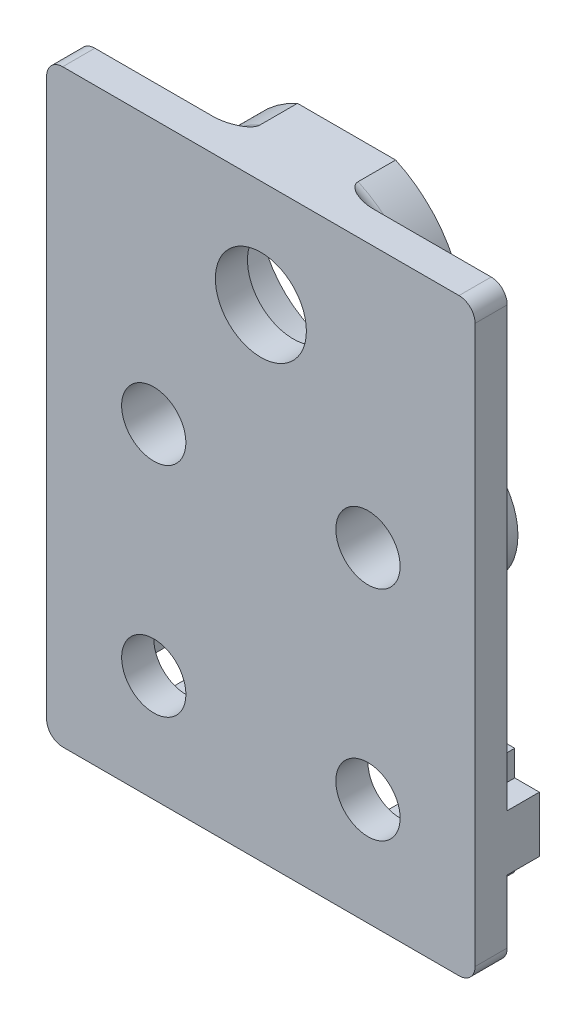
SolidWorks part; units mm, degrees
ref_plane "前视基准面" through (0, 0, 0) normal (0, 0, 1) x (1, 0, 0)
ref_plane "上视基准面" through (0, 0, 0) normal (0, 1, 0) x (1, 0, 0)
ref_plane "右视基准面" through (0, 0, 0) normal (1, 0, 0) x (0, 0, -1)
sketch "草图1" plane through (0, 0, 0) normal (0, 0, 1) x (1, 0, 0)
  line L0 (-20, 0) -> (-20, -6.9)
  line L1 (-20, 0) -> (-13.1, 0)
  line L4 (-6.9, -1.8) -> (-6.9, 0)
  line L5 (-13.1, -1.8) -> (-13.1, 0)
  line L6 (-4.5, -3.4393) -> (-4.5, -1.8)
  line L7 (-4.5, -3.4393) -> (-7.1607, -6.1)
  line L8 (-3.4393, -4.5) -> (-6.1, -7.1607)
  line L9 (-16.5607, -4.5) -> (-18.2, -4.5)
  line L10 (-13.1, -1.8) -> (-15.5, -1.8)
  line L11 (-6.9, 0) -> (0, 0)
  line L12 (-12.8393, -13.9) -> (-7.1607, -13.9)
  line L13 (-13.9, -12.8393) -> (-13.9, -7.1607)
  line L14 (-12.8393, -6.1) -> (-7.1607, -6.1)
  line L15 (-6.1, -12.8393) -> (-6.1, -7.1607)
  line L16 (-10, -6.1) -> (-10, -13.9) construction
  line L17 (-13.9, -10) -> (-6.1, -10) construction
  line L18 (-6.9, -1.8) -> (-4.5, -1.8)
  line L19 (-16.5607, -4.5) -> (-13.9, -7.1607)
  line L20 (-15.5, -3.4393) -> (-12.8393, -6.1)
  line L21 (-15.5, -3.4393) -> (-15.5, -1.8)
  line L22 (-18.2, -6.9) -> (-18.2, -4.5)
  line L23 (-18.2, -6.9) -> (-20, -6.9)
  line L24 (-18.2, -13.1) -> (-20, -13.1)
  line L25 (-18.2, -13.1) -> (-18.2, -15.5)
  line L26 (-15.5, -16.5607) -> (-15.5, -18.2)
  line L27 (-15.5, -16.5607) -> (-12.8393, -13.9)
  line L28 (-16.5607, -15.5) -> (-13.9, -12.8393)
  line L29 (-6.9, -18.2) -> (-4.5, -18.2)
  line L30 (-6.9, -20) -> (0, -20)
  line L31 (-13.1, -18.2) -> (-15.5, -18.2)
  line L32 (-16.5607, -15.5) -> (-18.2, -15.5)
  line L33 (-3.4393, -15.5) -> (-6.1, -12.8393)
  line L34 (-4.5, -16.5607) -> (-7.1607, -13.9)
  line L35 (-4.5, -16.5607) -> (-4.5, -18.2)
  line L36 (-13.1, -18.2) -> (-13.1, -20)
  line L37 (-6.9, -18.2) -> (-6.9, -20)
  line L38 (-20, -20) -> (-13.1, -20)
  line L39 (-20, -20) -> (-20, -13.1)
  line L40 (0, 0) -> (6.9, 0)
  line L41 (18.2, -6.9) -> (20, -6.9)
  line L42 (13.1, -1.8) -> (13.1, 0)
  line L43 (6.9, -1.8) -> (6.9, 0)
  line L44 (20, 0) -> (20, -6.9)
  line L45 (18.2, -6.9) -> (18.2, -4.5)
  line L46 (15.5, -3.4393) -> (15.5, -1.8)
  line L47 (15.5, -3.4393) -> (12.8393, -6.1)
  line L48 (16.5607, -4.5) -> (13.9, -7.1607)
  line L49 (6.9, -1.8) -> (4.5, -1.8)
  line L50 (13.1, 0) -> (20, 0)
  line L51 (7.1607, -13.9) -> (12.8393, -13.9)
  line L52 (6.1, -12.8393) -> (6.1, -7.1607)
  line L53 (7.1607, -6.1) -> (12.8393, -6.1)
  line L54 (13.9, -12.8393) -> (13.9, -7.1607)
  line L55 (13.1, -1.8) -> (15.5, -1.8)
  line L56 (16.5607, -4.5) -> (18.2, -4.5)
  line L57 (3.4393, -4.5) -> (6.1, -7.1607)
  line L58 (4.5, -3.4393) -> (7.1607, -6.1)
  line L59 (4.5, -3.4393) -> (4.5, -1.8)
  line L60 (4.5, -16.5607) -> (4.5, -18.2)
  line L61 (4.5, -16.5607) -> (7.1607, -13.9)
  line L62 (3.4393, -15.5) -> (6.1, -12.8393)
  line L63 (16.5607, -15.5) -> (18.2, -15.5)
  line L64 (13.1, -18.2) -> (15.5, -18.2)
  line L65 (13.1, -20) -> (20, -20)
  line L66 (6.9, -18.2) -> (4.5, -18.2)
  line L67 (16.5607, -15.5) -> (13.9, -12.8393)
  line L68 (15.5, -16.5607) -> (12.8393, -13.9)
  line L69 (15.5, -16.5607) -> (15.5, -18.2)
  line L70 (18.2, -13.1) -> (18.2, -15.5)
  line L71 (20, -20) -> (20, -13.1)
  line L72 (6.9, -18.2) -> (6.9, -20)
  line L73 (13.1, -18.2) -> (13.1, -20)
  line L74 (18.2, -13.1) -> (20, -13.1)
  line L75 (0, -20) -> (6.9, -20)
  line L78 (10, -6.1) -> (10, -13.9) construction
  line L79 (6.1, -10) -> (13.9, -10) construction
  line L80 (3.4393, -1.8) -> (-3.4393, -1.8)
  line L81 (-3.4393, -1.8) -> (-3.4393, -4.5)
  line L82 (3.4393, -1.8) -> (3.4393, -4.5)
  line L83 (-3.4393, -18.2) -> (-3.4393, -15.5)
  line L84 (3.4393, -18.2) -> (3.4393, -15.5)
  line L85 (3.4393, -18.2) -> (-3.4393, -18.2)
  circle A0 centre (-10, -10) radius 2.55
  circle A1 centre (10, -10) radius 2.55
  point P0 (-10, -10)
  point P8 (-10, -1.8)
  point P9 (-9.8043, -1.8)
  point P13 (-10, -1.8)
  point P20 (-5, -5)
  point P33 (-15, -5)
  point P50 (-15, -15)
  point P51 (-5, -15)
  point P52 (-10, -18.2)
  point P53 (-9.8043, -18.2)
  point P54 (10, -10)
  point P58 (10, -1.8)
  point P59 (10.1957, -1.8)
  point P63 (10, -1.8)
  point P70 (15, -5)
  point P83 (5, -5)
  point P102 (5, -15)
  point P103 (15, -15)
  point P104 (10, -18.2)
  point P105 (10.1957, -18.2)
extrude "凸台-拉伸1" add sketch "草图1" along normal blind 10
sketch "草图2" plane through (0, 0, 10) normal (0, 0, 1) x (1, 0, 0)
  line L1 (-20, 0) -> (20, 0)
  line L2 (-20, 0) -> (-20, -20)
  line L3 (-20, -20) -> (20, -20)
  line L4 (20, 0) -> (20, -20)
extrude "凸台-拉伸2" add sketch "草图2" along normal blind 3
sketch "草图3" plane through (0, 0, 10) normal (0, 0, -1) x (-1, 0, 0)
  line L0 (-13.1, -20) -> (-6.9, -20) construction
  line L1 (-6.9, -20) -> (-6.9, -18.2) construction
  line L2 (-6.9, -18.2) -> (-4.5, -18.2) construction
  line L3 (-4.5, -18.2) -> (-4.5, -16.5607) construction
  line L4 (-4.5, -16.5607) -> (-7.1607, -13.9) construction
  line L5 (-7.1607, -13.9) -> (-12.8393, -13.9) construction
  line L6 (-12.8393, -13.9) -> (-15.5, -16.5607) construction
  line L7 (-15.5, -16.5607) -> (-15.5, -18.2) construction
  line L8 (-15.5, -18.2) -> (-13.1, -18.2) construction
  line L9 (-13.1, -18.2) -> (-13.1, -20) construction
  line L10 (-20, -6.9) -> (-20, -13.1) construction
  line L11 (-20, -13.1) -> (-18.2, -13.1) construction
  line L12 (-18.2, -13.1) -> (-18.2, -15.5) construction
  line L13 (-18.2, -15.5) -> (-16.5607, -15.5) construction
  line L14 (-16.5607, -15.5) -> (-13.9, -12.8393) construction
  line L15 (-13.9, -12.8393) -> (-13.9, -7.1607) construction
  line L16 (-13.9, -7.1607) -> (-16.5607, -4.5) construction
  line L17 (-16.5607, -4.5) -> (-18.2, -4.5) construction
  line L18 (-18.2, -4.5) -> (-18.2, -6.9) construction
  line L19 (-18.2, -6.9) -> (-20, -6.9) construction
  line L20 (-6.9, 0) -> (-13.1, 0) construction
  line L21 (-13.1, 0) -> (-13.1, -1.8) construction
  line L22 (-13.1, -1.8) -> (-15.5, -1.8) construction
  line L23 (-15.5, -1.8) -> (-15.5, -3.4393) construction
  line L24 (-15.5, -3.4393) -> (-12.8393, -6.1) construction
  line L25 (-12.8393, -6.1) -> (-7.1607, -6.1) construction
  line L26 (-7.1607, -6.1) -> (-4.5, -3.4393) construction
  line L27 (-4.5, -3.4393) -> (-4.5, -1.8) construction
  line L28 (-4.5, -1.8) -> (-6.9, -1.8) construction
  line L29 (-6.9, -1.8) -> (-6.9, 0) construction
  line L30 (6.9, -20) -> (13.1, -20) construction
  line L31 (13.1, -20) -> (13.1, -18.2) construction
  line L32 (13.1, -18.2) -> (15.5, -18.2) construction
  line L33 (15.5, -18.2) -> (15.5, -16.5607) construction
  line L34 (15.5, -16.5607) -> (12.8393, -13.9) construction
  line L35 (12.8393, -13.9) -> (7.1607, -13.9) construction
  line L36 (7.1607, -13.9) -> (4.5, -16.5607) construction
  line L37 (4.5, -16.5607) -> (4.5, -18.2) construction
  line L38 (4.5, -18.2) -> (6.9, -18.2) construction
  line L39 (6.9, -18.2) -> (6.9, -20) construction
  line L40 (20, -13.1) -> (20, -6.9) construction
  line L41 (20, -6.9) -> (18.2, -6.9) construction
  line L42 (18.2, -6.9) -> (18.2, -4.5) construction
  line L43 (18.2, -4.5) -> (16.5607, -4.5) construction
  line L44 (16.5607, -4.5) -> (13.9, -7.1607) construction
  line L45 (13.9, -7.1607) -> (13.9, -12.8393) construction
  line L46 (13.9, -12.8393) -> (16.5607, -15.5) construction
  line L47 (16.5607, -15.5) -> (18.2, -15.5) construction
  line L48 (18.2, -15.5) -> (18.2, -13.1) construction
  line L49 (18.2, -13.1) -> (20, -13.1) construction
  line L50 (13.1, 0) -> (6.9, 0) construction
  line L51 (6.9, 0) -> (6.9, -1.8) construction
  line L52 (6.9, -1.8) -> (4.5, -1.8) construction
  line L53 (4.5, -1.8) -> (4.5, -3.4393) construction
  line L54 (4.5, -3.4393) -> (7.1607, -6.1) construction
  line L55 (7.1607, -6.1) -> (12.8393, -6.1) construction
  line L56 (12.8393, -6.1) -> (15.5, -3.4393) construction
  line L57 (15.5, -3.4393) -> (15.5, -1.8) construction
  line L58 (15.5, -1.8) -> (13.1, -1.8) construction
  line L59 (13.1, -1.8) -> (13.1, 0) construction
  line L60 (-13.1, -20) -> (-6.9, -20)
  line L61 (-6.9, -20) -> (-6.9, -18.2)
  line L62 (-6.9, -18.2) -> (-4.5, -18.2)
  line L63 (-4.5, -18.2) -> (-4.5, -16.5607)
  line L64 (-4.5, -16.5607) -> (-7.1607, -13.9)
  line L65 (-7.1607, -13.9) -> (-12.8393, -13.9)
  line L66 (-12.8393, -13.9) -> (-15.5, -16.5607)
  line L67 (-15.5, -16.5607) -> (-15.5, -18.2)
  line L68 (-15.5, -18.2) -> (-13.1, -18.2)
  line L69 (-13.1, -18.2) -> (-13.1, -20)
  line L70 (-20, -6.9) -> (-20, -13.1)
  line L71 (-20, -13.1) -> (-18.2, -13.1)
  line L72 (-18.2, -13.1) -> (-18.2, -15.5)
  line L73 (-18.2, -15.5) -> (-16.5607, -15.5)
  line L74 (-16.5607, -15.5) -> (-13.9, -12.8393)
  line L75 (-13.9, -12.8393) -> (-13.9, -7.1607)
  line L76 (-13.9, -7.1607) -> (-16.5607, -4.5)
  line L77 (-16.5607, -4.5) -> (-18.2, -4.5)
  line L78 (-18.2, -4.5) -> (-18.2, -6.9)
  line L79 (-18.2, -6.9) -> (-20, -6.9)
  line L80 (-6.9, 0) -> (-13.1, 0)
  line L81 (-13.1, 0) -> (-13.1, -1.8)
  line L82 (-13.1, -1.8) -> (-15.5, -1.8)
  line L83 (-15.5, -1.8) -> (-15.5, -3.4393)
  line L84 (-15.5, -3.4393) -> (-12.8393, -6.1)
  line L85 (-12.8393, -6.1) -> (-7.1607, -6.1)
  line L86 (-7.1607, -6.1) -> (-4.5, -3.4393)
  line L87 (-4.5, -3.4393) -> (-4.5, -1.8)
  line L88 (-4.5, -1.8) -> (-6.9, -1.8)
  line L89 (-6.9, -1.8) -> (-6.9, 0)
  line L90 (6.9, -20) -> (13.1, -20)
  line L91 (13.1, -20) -> (13.1, -18.2)
  line L92 (13.1, -18.2) -> (15.5, -18.2)
  line L93 (15.5, -18.2) -> (15.5, -16.5607)
  line L94 (15.5, -16.5607) -> (12.8393, -13.9)
  line L95 (12.8393, -13.9) -> (7.1607, -13.9)
  line L96 (7.1607, -13.9) -> (4.5, -16.5607)
  line L97 (4.5, -16.5607) -> (4.5, -18.2)
  line L98 (4.5, -18.2) -> (6.9, -18.2)
  line L99 (6.9, -18.2) -> (6.9, -20)
  line L100 (20, -13.1) -> (20, -6.9)
  line L101 (20, -6.9) -> (18.2, -6.9)
  line L102 (18.2, -6.9) -> (18.2, -4.5)
  line L103 (18.2, -4.5) -> (16.5607, -4.5)
  line L104 (16.5607, -4.5) -> (13.9, -7.1607)
  line L105 (13.9, -7.1607) -> (13.9, -12.8393)
  line L106 (13.9, -12.8393) -> (16.5607, -15.5)
  line L107 (16.5607, -15.5) -> (18.2, -15.5)
  line L108 (18.2, -15.5) -> (18.2, -13.1)
  line L109 (18.2, -13.1) -> (20, -13.1)
  line L110 (13.1, 0) -> (6.9, 0)
  line L111 (6.9, 0) -> (6.9, -1.8)
  line L112 (6.9, -1.8) -> (4.5, -1.8)
  line L113 (4.5, -1.8) -> (4.5, -3.4393)
  line L114 (4.5, -3.4393) -> (7.1607, -6.1)
  line L115 (7.1607, -6.1) -> (12.8393, -6.1)
  line L116 (12.8393, -6.1) -> (15.5, -3.4393)
  line L117 (15.5, -3.4393) -> (15.5, -1.8)
  line L118 (15.5, -1.8) -> (13.1, -1.8)
  line L119 (13.1, -1.8) -> (13.1, 0)
extrude "凸台-拉伸3" add sketch "草图3" along normal blind 3
sketch "草图4" plane through (0, 0, 0) normal (0, 0, -1) x (-1, 0, 0)
  line L64 (6.9, 0) -> (-6.9, 0)
  line L65 (-6.9, 0) -> (-6.9, -1.8)
  line L66 (-6.9, -1.8) -> (-4.5, -1.8)
  line L67 (-4.5, -1.8) -> (-4.5, -3.4393)
  line L68 (-4.5, -3.4393) -> (-7.1607, -6.1)
  line L69 (-7.1607, -6.1) -> (-12.8393, -6.1)
  line L70 (-12.8393, -6.1) -> (-15.5, -3.4393)
  line L71 (-15.5, -3.4393) -> (-15.5, -1.8)
  line L72 (-15.5, -1.8) -> (-13.1, -1.8)
  line L73 (-13.1, -1.8) -> (-13.1, 0)
  line L74 (-13.1, 0) -> (-20, 0)
  line L75 (-20, 0) -> (-20, -6.9)
  line L76 (-20, -6.9) -> (-18.2, -6.9)
  line L77 (-18.2, -6.9) -> (-18.2, -4.5)
  line L78 (-18.2, -4.5) -> (-16.5607, -4.5)
  line L79 (-16.5607, -4.5) -> (-13.9, -7.1607)
  line L80 (-13.9, -7.1607) -> (-13.9, -12.8393)
  line L81 (-13.9, -12.8393) -> (-16.5607, -15.5)
  line L82 (-16.5607, -15.5) -> (-18.2, -15.5)
  line L83 (-18.2, -15.5) -> (-18.2, -13.1)
  line L84 (-18.2, -13.1) -> (-20, -13.1)
  line L85 (-20, -13.1) -> (-20, -20)
  line L86 (-20, -20) -> (-13.1, -20)
  line L87 (-13.1, -20) -> (-13.1, -18.2)
  line L88 (-13.1, -18.2) -> (-15.5, -18.2)
  line L89 (-15.5, -18.2) -> (-15.5, -16.5607)
  line L90 (-15.5, -16.5607) -> (-12.8393, -13.9)
  line L91 (-12.8393, -13.9) -> (-7.1607, -13.9)
  line L92 (-7.1607, -13.9) -> (-4.5, -16.5607)
  line L93 (-4.5, -16.5607) -> (-4.5, -18.2)
  line L94 (-4.5, -18.2) -> (-6.9, -18.2)
  line L95 (-6.9, -18.2) -> (-6.9, -20)
  line L96 (-6.9, -20) -> (6.9, -20)
  line L97 (6.9, -20) -> (6.9, -18.2)
  line L98 (6.9, -18.2) -> (4.5, -18.2)
  line L99 (4.5, -18.2) -> (4.5, -16.5607)
  line L100 (4.5, -16.5607) -> (7.1607, -13.9)
  line L101 (7.1607, -13.9) -> (12.8393, -13.9)
  line L102 (12.8393, -13.9) -> (15.5, -16.5607)
  line L103 (15.5, -16.5607) -> (15.5, -18.2)
  line L104 (15.5, -18.2) -> (13.1, -18.2)
  line L105 (13.1, -18.2) -> (13.1, -20)
  line L106 (13.1, -20) -> (20, -20)
  line L107 (20, -20) -> (20, -13.1)
  line L108 (20, -13.1) -> (18.2, -13.1)
  line L109 (18.2, -13.1) -> (18.2, -15.5)
  line L110 (18.2, -15.5) -> (16.5607, -15.5)
  line L111 (16.5607, -15.5) -> (13.9, -12.8393)
  line L112 (13.9, -12.8393) -> (13.9, -7.1607)
  line L113 (13.9, -7.1607) -> (16.5607, -4.5)
  line L114 (16.5607, -4.5) -> (18.2, -4.5)
  line L115 (18.2, -4.5) -> (18.2, -6.9)
  line L116 (18.2, -6.9) -> (20, -6.9)
  line L117 (20, -6.9) -> (20, 0)
  line L118 (20, 0) -> (13.1, 0)
  line L119 (13.1, 0) -> (13.1, -1.8)
  line L120 (13.1, -1.8) -> (15.5, -1.8)
  line L121 (15.5, -1.8) -> (15.5, -3.4393)
  line L122 (15.5, -3.4393) -> (12.8393, -6.1)
  line L123 (12.8393, -6.1) -> (7.1607, -6.1)
  line L124 (7.1607, -6.1) -> (4.5, -3.4393)
  line L125 (4.5, -3.4393) -> (4.5, -1.8)
  line L126 (4.5, -1.8) -> (6.9, -1.8)
  line L127 (6.9, -1.8) -> (6.9, 0)
  line L128 (6.9, 0) -> (-6.9, 0)
  line L129 (-6.9, 0) -> (-6.9, -1.8)
  line L130 (-6.9, -1.8) -> (-4.5, -1.8)
  line L131 (-4.5, -1.8) -> (-4.5, -3.4393)
  line L132 (-4.5, -3.4393) -> (-7.1607, -6.1)
  line L133 (-7.1607, -6.1) -> (-12.8393, -6.1)
  line L134 (-12.8393, -6.1) -> (-15.5, -3.4393)
  line L135 (-15.5, -3.4393) -> (-15.5, -1.8)
  line L136 (-15.5, -1.8) -> (-13.1, -1.8)
  line L137 (-13.1, -1.8) -> (-13.1, 0)
  line L138 (-13.1, 0) -> (-20, 0)
  line L139 (-20, 0) -> (-20, -6.9)
  line L140 (-20, -6.9) -> (-18.2, -6.9)
  line L141 (-18.2, -6.9) -> (-18.2, -4.5)
  line L142 (-18.2, -4.5) -> (-16.5607, -4.5)
  line L143 (-16.5607, -4.5) -> (-13.9, -7.1607)
  line L144 (-13.9, -7.1607) -> (-13.9, -12.8393)
  line L145 (-13.9, -12.8393) -> (-16.5607, -15.5)
  line L146 (-16.5607, -15.5) -> (-18.2, -15.5)
  line L147 (-18.2, -15.5) -> (-18.2, -13.1)
  line L148 (-18.2, -13.1) -> (-20, -13.1)
  line L149 (-20, -13.1) -> (-20, -20)
  line L150 (-20, -20) -> (-13.1, -20)
  line L151 (-13.1, -20) -> (-13.1, -18.2)
  line L152 (-13.1, -18.2) -> (-15.5, -18.2)
  line L153 (-15.5, -18.2) -> (-15.5, -16.5607)
  line L154 (-15.5, -16.5607) -> (-12.8393, -13.9)
  line L155 (-12.8393, -13.9) -> (-7.1607, -13.9)
  line L156 (-7.1607, -13.9) -> (-4.5, -16.5607)
  line L157 (-4.5, -16.5607) -> (-4.5, -18.2)
  line L158 (-4.5, -18.2) -> (-6.9, -18.2)
  line L159 (-6.9, -18.2) -> (-6.9, -20)
  line L160 (-6.9, -20) -> (6.9, -20)
  line L161 (6.9, -20) -> (6.9, -18.2)
  line L162 (6.9, -18.2) -> (4.5, -18.2)
  line L163 (4.5, -18.2) -> (4.5, -16.5607)
  line L164 (4.5, -16.5607) -> (7.1607, -13.9)
  line L165 (7.1607, -13.9) -> (12.8393, -13.9)
  line L166 (12.8393, -13.9) -> (15.5, -16.5607)
  line L167 (15.5, -16.5607) -> (15.5, -18.2)
  line L168 (15.5, -18.2) -> (13.1, -18.2)
  line L169 (13.1, -18.2) -> (13.1, -20)
  line L170 (13.1, -20) -> (20, -20)
  line L171 (20, -20) -> (20, -13.1)
  line L172 (20, -13.1) -> (18.2, -13.1)
  line L173 (18.2, -13.1) -> (18.2, -15.5)
  line L174 (18.2, -15.5) -> (16.5607, -15.5)
  line L175 (16.5607, -15.5) -> (13.9, -12.8393)
  line L176 (13.9, -12.8393) -> (13.9, -7.1607)
  line L177 (13.9, -7.1607) -> (16.5607, -4.5)
  line L178 (16.5607, -4.5) -> (18.2, -4.5)
  line L179 (18.2, -4.5) -> (18.2, -6.9)
  line L180 (18.2, -6.9) -> (20, -6.9)
  line L181 (20, -6.9) -> (20, 0)
  line L182 (20, 0) -> (13.1, 0)
  line L183 (13.1, 0) -> (13.1, -1.8)
  line L184 (13.1, -1.8) -> (15.5, -1.8)
  line L185 (15.5, -1.8) -> (15.5, -3.4393)
  line L186 (15.5, -3.4393) -> (12.8393, -6.1)
  line L187 (12.8393, -6.1) -> (7.1607, -6.1)
  line L188 (7.1607, -6.1) -> (4.5, -3.4393)
  line L189 (4.5, -3.4393) -> (4.5, -1.8)
  line L190 (4.5, -1.8) -> (6.9, -1.8)
  line L191 (6.9, -1.8) -> (6.9, 0)
  dimension "D1" = 0
extrude "切除-拉伸1" cut sketch "草图4" against normal blind 10
sketch "草图5" plane through (0, 0, 10) normal (0, 0, -1) x (-1, 0, 0)
  circle A0 centre (-10, -10) radius 3
  circle A1 centre (10, -10) radius 3
extrude "切除-拉伸2" cut sketch "草图5" against normal blind 10
sketch "草图6" plane through (0, 0, 13) normal (0, 0, 1) x (1, 0, 0)
  line L0 (-20, 0) -> (20, 0)
  line L1 (0, 35) -> (-20, 35)
  line L2 (-20, 35) -> (-20, 0)
  line L3 (20, 0) -> (20, 35)
  line L4 (0, 35) -> (20, 35)
  circle A0 centre (-10, 10.36) radius 3
  circle A1 centre (10, 10.36) radius 3
  circle A2 centre (0, 25) radius 4.25
extrude "凸台-拉伸4" add sketch "草图6" against normal blind 3
fillet "圆角1" radius 1.5 4 edges at (-20, -20, 11.5) (-20, 35, 11.5) (20, -20, 11.5) (20, 35, 11.5)
sketch "草图7" plane through (0, 0, 10) normal (0, 0, -1) x (-1, 0, 0)
  circle A1 centre (10, 10.36) radius 3 construction
  circle A2 centre (-10, 10.36) radius 3 construction
  circle A4 centre (10, 10.36) radius 3
  circle A5 centre (-10, 10.36) radius 3
  circle A6 centre (-10, 10.36) radius 6
  circle A7 centre (10, 10.36) radius 6
  dimension "D1" = 3
extrude "凸台-拉伸5" add sketch "草图7" along normal blind 5
sketch "草图8" plane through (0, 0, 10) normal (0, 0, -1) x (-1, 0, 0)
  line L0 (-4.5826, 35) -> (4.5826, 35)
  line L1 (-18.5, 35) -> (18.5, 35) construction
  circle A0 centre (0, 25) radius 8.25
  arc A1 (-4.5826, 35) -> (4.5826, 35) centre (0, 25) ccw
extrude "凸台-拉伸6" add sketch "草图8" along normal blind 5
fillet "圆角3" radius 1.5 3 edges at (-4, 10.36, 10) (16, 10.36, 10) (0, 14, 10)
sketch "草图9" plane through (0, 0, 7) normal (0, 0, -1) x (-1, 0, 0)
  line L0 (6.9, -18.2) -> (6.9, -20) construction
  line L1 (6.9, -20) -> (13.1, -20) construction
  line L2 (13.1, -20) -> (13.1, -18.2) construction
  line L3 (13.1, -18.2) -> (15.5, -18.2) construction
  line L4 (15.5, -18.2) -> (15.5, -16.5607) construction
  line L5 (15.5, -16.5607) -> (12.8393, -13.9) construction
  line L6 (12.8393, -13.9) -> (7.1607, -13.9) construction
  line L7 (7.1607, -13.9) -> (4.5, -16.5607) construction
  line L8 (4.5, -16.5607) -> (4.5, -18.2) construction
  line L9 (4.5, -18.2) -> (6.9, -18.2) construction
  line L10 (18.2, -13.1) -> (20, -13.1) construction
  line L11 (20, -13.1) -> (20, -6.9) construction
  line L12 (20, -6.9) -> (18.2, -6.9) construction
  line L13 (18.2, -6.9) -> (18.2, -4.5) construction
  line L14 (18.2, -4.5) -> (16.5607, -4.5) construction
  line L15 (16.5607, -4.5) -> (13.9, -7.1607) construction
  line L16 (13.9, -7.1607) -> (13.9, -12.8393) construction
  line L17 (13.9, -12.8393) -> (16.5607, -15.5) construction
  line L18 (16.5607, -15.5) -> (18.2, -15.5) construction
  line L19 (18.2, -15.5) -> (18.2, -13.1) construction
  line L20 (13.1, -1.8) -> (13.1, 0) construction
  line L21 (13.1, 0) -> (6.9, 0) construction
  line L22 (6.9, 0) -> (6.9, -1.8) construction
  line L23 (6.9, -1.8) -> (4.5, -1.8) construction
  line L24 (4.5, -1.8) -> (4.5, -3.4393) construction
  line L25 (4.5, -3.4393) -> (7.1607, -6.1) construction
  line L26 (7.1607, -6.1) -> (12.8393, -6.1) construction
  line L27 (12.8393, -6.1) -> (15.5, -3.4393) construction
  line L28 (15.5, -3.4393) -> (15.5, -1.8) construction
  line L29 (15.5, -1.8) -> (13.1, -1.8) construction
  line L30 (-6.9, -1.8) -> (-6.9, 0) construction
  line L31 (-6.9, 0) -> (-13.1, 0) construction
  line L32 (-13.1, 0) -> (-13.1, -1.8) construction
  line L33 (-13.1, -1.8) -> (-15.5, -1.8) construction
  line L34 (-15.5, -1.8) -> (-15.5, -3.4393) construction
  line L35 (-15.5, -3.4393) -> (-12.8393, -6.1) construction
  line L36 (-12.8393, -6.1) -> (-7.1607, -6.1) construction
  line L37 (-7.1607, -6.1) -> (-4.5, -3.4393) construction
  line L38 (-4.5, -3.4393) -> (-4.5, -1.8) construction
  line L39 (-4.5, -1.8) -> (-6.9, -1.8) construction
  line L40 (-13.1, -18.2) -> (-13.1, -20) construction
  line L41 (-13.1, -20) -> (-6.9, -20) construction
  line L42 (-6.9, -20) -> (-6.9, -18.2) construction
  line L43 (-6.9, -18.2) -> (-4.5, -18.2) construction
  line L44 (-4.5, -18.2) -> (-4.5, -16.5607) construction
  line L45 (-4.5, -16.5607) -> (-7.1607, -13.9) construction
  line L46 (-7.1607, -13.9) -> (-12.8393, -13.9) construction
  line L47 (-12.8393, -13.9) -> (-15.5, -16.5607) construction
  line L48 (-15.5, -16.5607) -> (-15.5, -18.2) construction
  line L49 (-15.5, -18.2) -> (-13.1, -18.2) construction
  line L50 (-18.2, -6.9) -> (-20, -6.9) construction
  line L51 (-20, -6.9) -> (-20, -13.1) construction
  line L52 (-20, -13.1) -> (-18.2, -13.1) construction
  line L53 (-18.2, -13.1) -> (-18.2, -15.5) construction
  line L54 (-18.2, -15.5) -> (-16.5607, -15.5) construction
  line L55 (-16.5607, -15.5) -> (-13.9, -12.8393) construction
  line L56 (-13.9, -12.8393) -> (-13.9, -7.1607) construction
  line L57 (-13.9, -7.1607) -> (-16.5607, -4.5) construction
  line L58 (-16.5607, -4.5) -> (-18.2, -4.5) construction
  line L59 (-18.2, -4.5) -> (-18.2, -6.9) construction
  line L60 (6.9, -18.2) -> (6.9, -20)
  line L61 (6.9, -20) -> (7.4, -20)
  line L62 (13.1, -20) -> (13.1, -18.2)
  line L63 (13.1, -18.2) -> (15.5, -18.2)
  line L64 (15.5, -18.2) -> (15.5, -16.5607)
  line L65 (15.5, -16.5607) -> (12.8393, -13.9)
  line L66 (12.8393, -13.9) -> (7.1607, -13.9)
  line L67 (7.1607, -13.9) -> (4.5, -16.5607)
  line L68 (4.5, -16.5607) -> (4.5, -18.2)
  line L69 (4.5, -18.2) -> (6.9, -18.2)
  line L70 (18.2, -13.1) -> (20, -13.1)
  line L71 (20, -13.1) -> (20, -12.6)
  line L72 (20, -6.9) -> (18.2, -6.9)
  line L73 (18.2, -6.9) -> (18.2, -4.5)
  line L74 (18.2, -4.5) -> (16.5607, -4.5)
  line L75 (16.5607, -4.5) -> (13.9, -7.1607)
  line L76 (13.9, -7.1607) -> (13.9, -12.8393)
  line L77 (13.9, -12.8393) -> (16.5607, -15.5)
  line L78 (16.5607, -15.5) -> (18.2, -15.5)
  line L79 (18.2, -15.5) -> (18.2, -13.1)
  line L80 (13.1, -1.8) -> (13.1, 0)
  line L81 (13.1, 0) -> (12.6, 0)
  line L82 (6.9, 0) -> (6.9, -1.8)
  line L83 (6.9, -1.8) -> (4.5, -1.8)
  line L84 (4.5, -1.8) -> (4.5, -3.4393)
  line L85 (4.5, -3.4393) -> (7.1607, -6.1)
  line L86 (7.1607, -6.1) -> (12.8393, -6.1)
  line L87 (12.8393, -6.1) -> (15.5, -3.4393)
  line L88 (15.5, -3.4393) -> (15.5, -1.8)
  line L89 (15.5, -1.8) -> (13.1, -1.8)
  line L90 (-6.9, -1.8) -> (-6.9, 0)
  line L91 (-6.9, 0) -> (-7.4, 0)
  line L92 (-13.1, 0) -> (-13.1, -1.8)
  line L93 (-13.1, -1.8) -> (-15.5, -1.8)
  line L94 (-15.5, -1.8) -> (-15.5, -3.4393)
  line L95 (-15.5, -3.4393) -> (-12.8393, -6.1)
  line L96 (-12.8393, -6.1) -> (-7.1607, -6.1)
  line L97 (-7.1607, -6.1) -> (-4.5, -3.4393)
  line L98 (-4.5, -3.4393) -> (-4.5, -1.8)
  line L99 (-4.5, -1.8) -> (-6.9, -1.8)
  line L100 (-13.1, -18.2) -> (-13.1, -20)
  line L101 (-13.1, -20) -> (-12.6, -20)
  line L102 (-6.9, -20) -> (-6.9, -18.2)
  line L103 (-6.9, -18.2) -> (-4.5, -18.2)
  line L104 (-4.5, -18.2) -> (-4.5, -16.5607)
  line L105 (-4.5, -16.5607) -> (-7.1607, -13.9)
  line L106 (-7.1607, -13.9) -> (-12.8393, -13.9)
  line L107 (-12.8393, -13.9) -> (-15.5, -16.5607)
  line L108 (-15.5, -16.5607) -> (-15.5, -18.2)
  line L109 (-15.5, -18.2) -> (-13.1, -18.2)
  line L110 (-18.2, -6.9) -> (-20, -6.9)
  line L111 (-20, -6.9) -> (-20, -7.4)
  line L112 (-20, -13.1) -> (-18.2, -13.1)
  line L113 (-18.2, -13.1) -> (-18.2, -15.5)
  line L114 (-18.2, -15.5) -> (-16.5607, -15.5)
  line L115 (-16.5607, -15.5) -> (-13.9, -12.8393)
  line L116 (-13.9, -12.8393) -> (-13.9, -7.1607)
  line L117 (-13.9, -7.1607) -> (-16.5607, -4.5)
  line L118 (-16.5607, -4.5) -> (-18.2, -4.5)
  line L119 (-18.2, -4.5) -> (-18.2, -6.9)
  line L120 (-12.6, -17.7) -> (-12.6, -19.5)
  line L122 (-7.4, -19.5) -> (-7.4, -17.7)
  line L123 (-7.4, -17.7) -> (-5, -17.7)
  line L124 (-5, -17.7) -> (-5, -16.7678)
  line L125 (-5, -16.7678) -> (-7.3678, -14.4)
  line L126 (-7.3678, -14.4) -> (-12.6322, -14.4)
  line L127 (-12.6322, -14.4) -> (-15, -16.7678)
  line L128 (-15, -16.7678) -> (-15, -17.7)
  line L129 (-15, -17.7) -> (-12.6, -17.7)
  line L130 (-17.7, -7.4) -> (-19.5, -7.4)
  line L132 (-19.5, -12.6) -> (-17.7, -12.6)
  line L133 (-17.7, -12.6) -> (-17.7, -15)
  line L134 (-17.7, -15) -> (-16.7678, -15)
  line L135 (-16.7678, -15) -> (-14.4, -12.6322)
  line L136 (-14.4, -12.6322) -> (-14.4, -7.3678)
  line L137 (-14.4, -7.3678) -> (-16.7678, -5)
  line L138 (-16.7678, -5) -> (-17.7, -5)
  line L139 (-17.7, -5) -> (-17.7, -7.4)
  line L140 (-7.4, -2.3) -> (-7.4, -0.5)
  line L142 (-12.6, -0.5) -> (-12.6, -2.3)
  line L143 (-12.6, -2.3) -> (-15, -2.3)
  line L144 (-15, -2.3) -> (-15, -3.2322)
  line L145 (-15, -3.2322) -> (-12.6322, -5.6)
  line L146 (-12.6322, -5.6) -> (-7.3678, -5.6)
  line L147 (-7.3678, -5.6) -> (-5, -3.2322)
  line L148 (-5, -3.2322) -> (-5, -2.3)
  line L149 (-5, -2.3) -> (-7.4, -2.3)
  line L150 (12.6, -2.3) -> (12.6, -0.5)
  line L152 (7.4, -0.5) -> (7.4, -2.3)
  line L153 (7.4, -2.3) -> (5, -2.3)
  line L154 (5, -2.3) -> (5, -3.2322)
  line L155 (5, -3.2322) -> (7.3678, -5.6)
  line L156 (7.3678, -5.6) -> (12.6322, -5.6)
  line L157 (12.6322, -5.6) -> (15, -3.2322)
  line L158 (15, -3.2322) -> (15, -2.3)
  line L159 (15, -2.3) -> (12.6, -2.3)
  line L160 (17.7, -12.6) -> (19.5, -12.6)
  line L162 (19.5, -7.4) -> (17.7, -7.4)
  line L163 (17.7, -7.4) -> (17.7, -5)
  line L164 (17.7, -5) -> (16.7678, -5)
  line L165 (16.7678, -5) -> (14.4, -7.3678)
  line L166 (14.4, -7.3678) -> (14.4, -12.6322)
  line L167 (14.4, -12.6322) -> (16.7678, -15)
  line L168 (16.7678, -15) -> (17.7, -15)
  line L169 (17.7, -15) -> (17.7, -12.6)
  line L170 (7.4, -17.7) -> (7.4, -19.5)
  line L172 (12.6, -19.5) -> (12.6, -17.7)
  line L173 (12.6, -17.7) -> (15, -17.7)
  line L174 (15, -17.7) -> (15, -16.7678)
  line L175 (15, -16.7678) -> (12.6322, -14.4)
  line L176 (12.6322, -14.4) -> (7.3678, -14.4)
  line L177 (7.3678, -14.4) -> (5, -16.7678)
  line L178 (5, -16.7678) -> (5, -17.7)
  line L179 (5, -17.7) -> (7.4, -17.7)
  line L180 (-19.5, -12.6) -> (-20, -12.6)
  line L181 (-19.5, -7.4) -> (-20, -7.4)
  line L182 (-12.6, -19.5) -> (-12.6, -20)
  line L183 (-7.4, -19.5) -> (-7.4, -20)
  line L184 (-7.4, -0.5) -> (-7.4, 0)
  line L185 (-12.6, -0.5) -> (-12.6, 0)
  line L186 (7.4, -0.5) -> (7.4, 0)
  line L187 (12.6, -0.5) -> (12.6, 0)
  line L188 (19.5, -7.4) -> (20, -7.4)
  line L189 (19.5, -12.6) -> (20, -12.6)
  line L190 (7.4, -19.5) -> (7.4, -20)
  line L191 (12.6, -19.5) -> (12.6, -20)
  line L192 (12.6, -20) -> (13.1, -20)
  line L193 (20, -7.4) -> (20, -6.9)
  line L194 (7.4, -19.5) -> (12.6, -19.5) construction
  line L195 (6.9, -20) -> (13.1, -20) construction
  line L196 (7.4, 0) -> (6.9, 0)
  line L197 (20, -13.1) -> (20, -6.9) construction
  line L198 (19.5, -12.6) -> (19.5, -7.4) construction
  line L199 (12.6, -0.5) -> (7.4, -0.5) construction
  line L200 (-20, -12.6) -> (-20, -13.1)
  line L201 (13.1, 0) -> (6.9, 0) construction
  line L202 (-19.5, -7.4) -> (-19.5, -12.6) construction
  line L203 (-12.6, 0) -> (-13.1, 0)
  line L204 (-20, -6.9) -> (-20, -13.1) construction
  line L205 (-7.4, -20) -> (-6.9, -20)
  line L206 (-6.9, 0) -> (-13.1, 0) construction
  line L207 (-7.4, -0.5) -> (-12.6, -0.5) construction
  line L208 (-12.6, -19.5) -> (-7.4, -19.5) construction
  line L210 (-13.1, -20) -> (-6.9, -20) construction
  dimension "D1" = 0.5
extrude "切除-拉伸3" cut sketch "草图9" against normal blind 3
